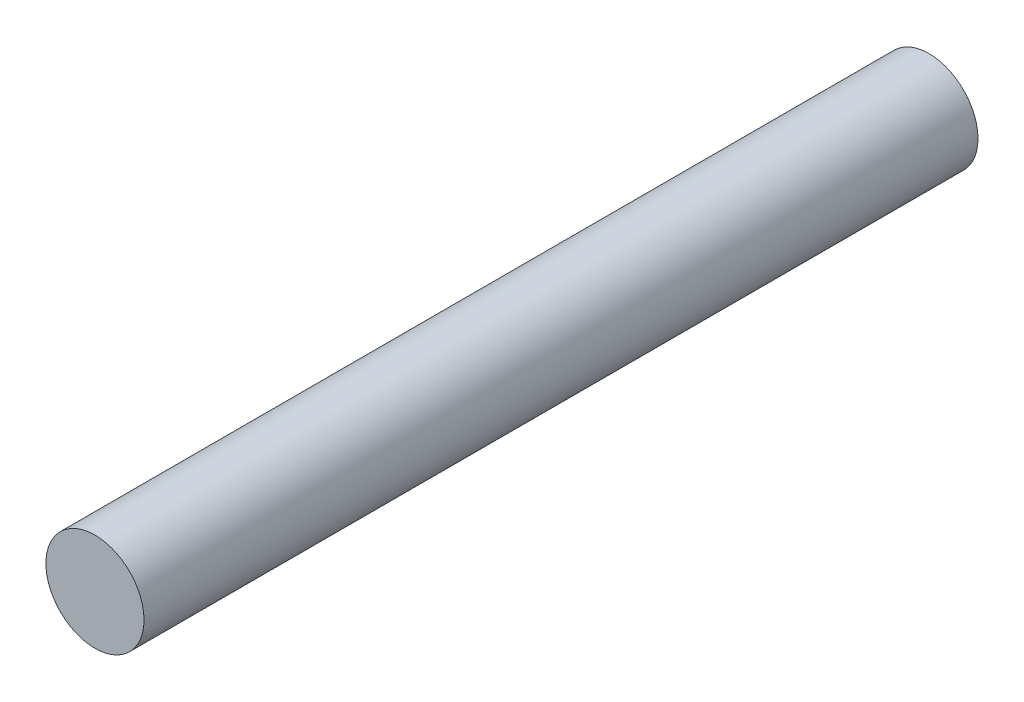
SolidWorks part; units mm, degrees
material "CF rod"
ref_plane "Front" through (0, 0, 0) normal (0, 0, 1) x (1, 0, 0)
ref_plane "Top" through (0, 0, 0) normal (0, 1, 0) x (1, 0, 0)
ref_plane "Right" through (0, 0, 0) normal (1, 0, 0) x (0, 0, -1)
sketch "Sketch1" plane through (0, 0, 0) normal (0, 0, 1) x (1, 0, 0)
  circle A0 centre (0, 0) radius 3.175
  dimension "D1" = 6.35
extrude "Boss-Extrude1" add sketch "Sketch1" along normal blind 53.975
equation "\"truss_member_od\" = .25in"
equation "\"truss_member_L1\" = 2.125in"
equation "\"connector_hole_depth\" = .375in"
equation "\"truss_member_L2\" = 3in"
equation "\"D1@Boss-Extrude1\"=\"truss_member_L1\""
equation "\"D1@Sketch1\"=\"truss_member_od\""
